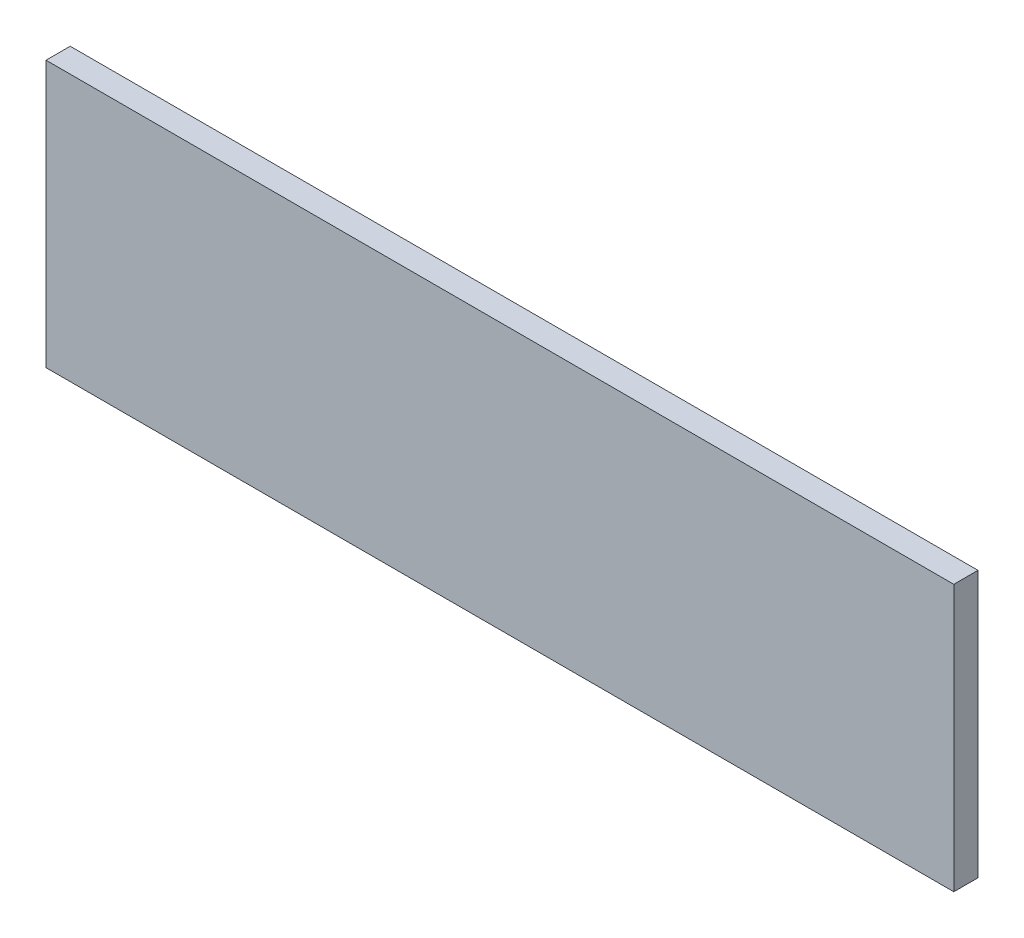
SolidWorks part; units mm, degrees
ref_plane "Plan de face" through (0, 0, 0) normal (0, 0, 1) x (1, 0, 0)
ref_plane "Plan de dessus" through (0, 0, 0) normal (0, 1, 0) x (1, 0, 0)
ref_plane "Plan de droite" through (0, 0, 0) normal (1, 0, 0) x (0, 0, -1)
sketch "Esquisse1" plane through (0, 0, 0) normal (0, 0, 1) x (1, 0, 0)
  line L1 (-36.1663, 22.3328) -> (113.8337, 22.3328)
  line L2 (-36.1663, 22.3328) -> (-36.1663, -21.6672)
  line L3 (-36.1663, -21.6672) -> (113.8337, -21.6672)
  line L4 (113.8337, 22.3328) -> (113.8337, -21.6672)
  dimension "D1" = 44
  dimension "D2" = 150
extrude "Boss.-Extru.1" add sketch "Esquisse1" along normal blind 4
